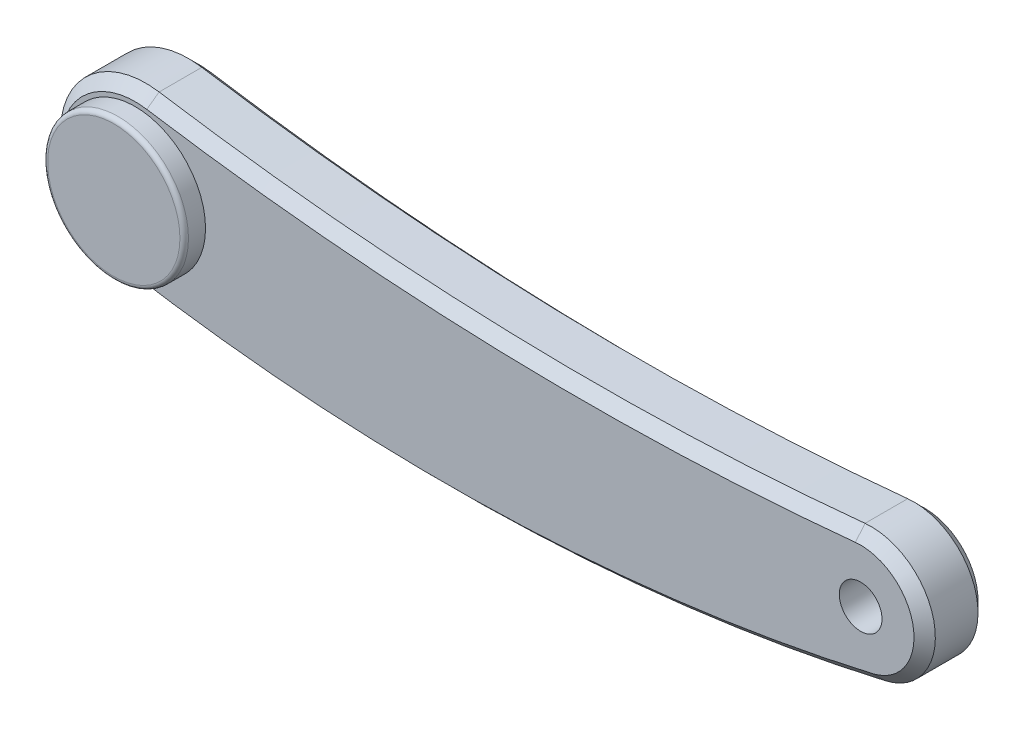
SolidWorks part; units mm, degrees
ref_plane "Front Plane" through (0, 0, 0) normal (0, 0, 1) x (1, 0, 0)
ref_plane "Top Plane" through (0, 0, 0) normal (0, 1, 0) x (1, 0, 0)
ref_plane "Right Plane" through (0, 0, 0) normal (1, 0, 0) x (0, 0, -1)
sketch "Sketch1" plane through (0, 0, 0) normal (0, 0, 1) x (1, 0, 0)
  line L0 (-85, 0) -> (85, 0) construction
  circle A0 centre (85, 0) radius 15
  circle A1 centre (-85, 0) radius 20
  arc A2 (-81.8766, 19.7546) -> (83.5255, 14.9274) centre (19.6324, 661.7795) ccw
  arc A3 (-88.3618, -19.7154) -> (88.3697, -14.6166) centre (-12.7206, 423.8817) ccw
  point P4 (0, 0)
  dimension "D2" = 40
  dimension "D3" = 30
  dimension "D4" = 450
  dimension "D5" = 650
  dimension "D1" = 170
extrude "Boss-Extrude1" add sketch "Sketch1" along normal mid plane 15 contours A1 | A1 L0 A0 A2 | L0 A1 A3 A0 | A0 region at (-1.2115, 6.9944, 0) region at (-72.4659, -14.8523, 0) region at (-0.4487, -12.3679, 0) region at (74.1987, 9.7869, 0)
chamfer "Chamfer1" distance 2.5 angle 45 8 edges at (99.8023, 2.427, -7.5) (0.6702, 12.0561, -7.5) (-104.7354, 3.2427, -7.5) (0.2568, -25.9311, -7.5) (-104.7354, 3.2427, 7.5) (0.6702, 12.0561, 7.5) (99.8023, 2.427, 7.5) (0.2568, -25.9311, 7.5)
sketch "Sketch2" plane through (0, 0, 7.5) normal (0, 0, 1) x (1, 0, 0)
  circle A0 centre (-85, 0) radius 16.5
  dimension "D1" = 33
extrude "Boss-Extrude2" add sketch "Sketch2" along normal blind 5
sketch "Sketch3" plane through (0, 0, 12.5) normal (0, 0, 1) x (1, 0, 0)
  line L0 (-85, 0) -> (-88.9097, 0)
  line L1 (-86.0119, 3.7765) -> (-83.9881, -3.7765)
  line L2 (-88.3859, -1.9548) -> (-85, 0)
  line L4 (-87.9055, 2.6161) -> (-85, 0)
  line L5 (-85, 0) -> (-86.2082, 3.7183)
  line L6 (-81.7211, 2.1294) -> (-88.2789, -2.1294)
  line L7 (-83.4098, 3.5717) -> (-85, 0)
  line L8 (-85, 0) -> (-81.837, 2.298)
  line L9 (-81.9616, -2.4604) -> (-88.0384, 2.4604)
  line L10 (-81.1117, -0.4087) -> (-85, 0)
  line L11 (-85, 0) -> (-81.837, -2.298)
  line L12 (-86.4011, -3.65) -> (-83.5989, 3.65)
  line L13 (-84.1871, -3.8242) -> (-85, 0)
  line L14 (-85, 0) -> (-86.2082, -3.7183)
  line L15 (-88.9043, 0.2046) -> (-81.0957, -0.2046)
  arc A0 (-86.0119, 3.7765) -> (-88.9097, 0) centre (-88.9097, 3) cw
  arc A1 (-83.9881, -3.7765) -> (-88.3859, -1.9548) centre (-86.8859, -4.5529) ccw
  arc A2 (-88.2789, -2.1294) -> (-87.9055, 2.6161) centre (-89.9128, 0.3866) ccw
  arc A3 (-81.7211, 2.1294) -> (-86.2082, 3.7183) centre (-83.355, 4.6454) cw
  arc A4 (-88.0384, 2.4604) -> (-83.4098, 3.5717) centre (-86.1504, 4.7919) ccw
  arc A5 (-81.9616, -2.4604) -> (-81.837, 2.298) centre (-80.0736, -0.129) cw
  arc A6 (-83.5989, 3.65) -> (-81.1117, -0.4087) centre (-80.7982, 2.5749) ccw
  arc A7 (-86.4011, -3.65) -> (-81.837, -2.298) centre (-83.6004, -4.7251) cw
  arc A8 (-81.0957, -0.2046) -> (-84.1871, -3.8242) centre (-81.2527, -3.2005) ccw
  arc A9 (-88.9043, 0.2046) -> (-86.2082, -3.7183) centre (-89.0613, -2.7913) cw
  circle A10 centre (-85, 0) radius 2
  point P10 (-85, 0)
  point P38 (-85, 0)
  circle M17 centre (-85, 0) radius 16.5
  dimension "D3" = 3
  dimension "D5" = 4
  dimension "D1" = 30
  dimension "D2" = 0
  dimension "D4" = 5
extrude "Boss-Extrude3" add sketch "Sketch3" against normal blind 5 contours A9 L15 A8 M17 | A10 L14 A9 A8 L13 M17 | L1 A1 M17 | A0 L1 M17 | A10 A1 L2 M17 | A10 L0 A0 M17 | A10 L5 A3 A2 L4 M17 | A3 L6 A2 M17 | A10 L8 A5 A4 L7 M17 | A5 L9 A4 M17 | A10 L11 A7 A6 L10 M17 | A7 L12 A6 M17 | A10 region at (-101.0333, 0, 12.5)
fillet "Fillet1" radius 1 1 edges at (-68.5, 0, 12.5)
sketch "Sketch4" plane through (0, 0, 7.5) normal (0, 0, 1) x (1, 0, 0)
  circle A0 centre (85, 0) radius 5
  dimension "D1" = 10
extrude "Cut-Extrude1" cut sketch "Sketch4" against normal blind 10
sketch "Sketch5" plane through (0, 0, -7.5) normal (0, 0, -1) x (-1, 0, 0)
  circle A0 centre (85, 0) radius 5
  dimension "D1" = 10
extrude "Boss-Extrude4" add sketch "Sketch5" along normal blind 10
